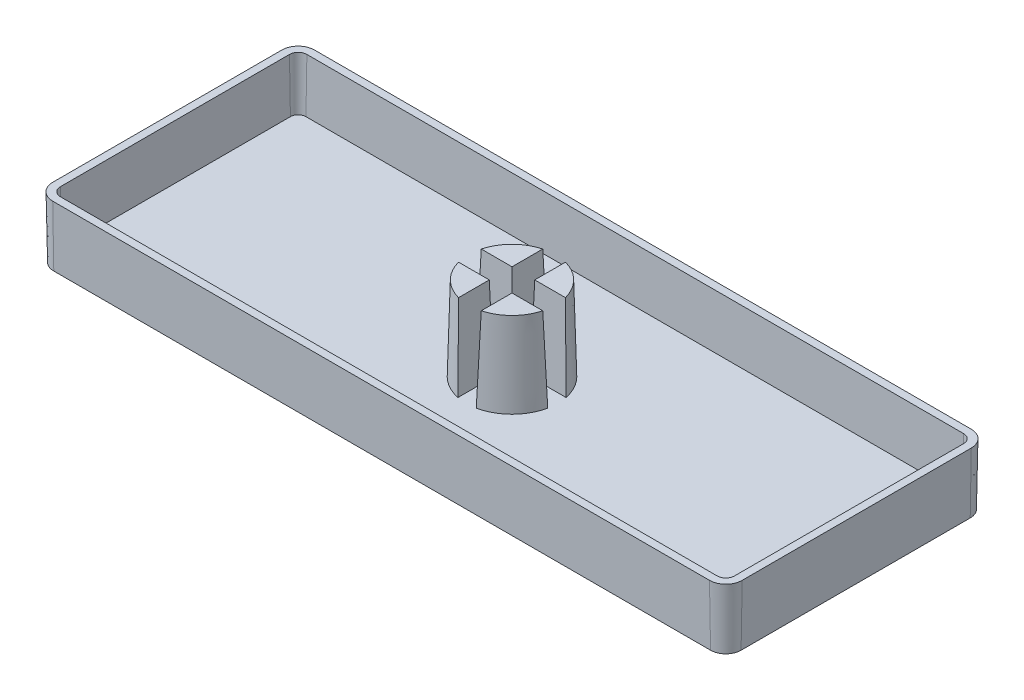
SolidWorks part; units mm, degrees
ref_plane "Front Plane" through (0, 0, 0) normal (0, 0, 1) x (1, 0, 0)
ref_plane "Top Plane" through (0, 0, 0) normal (0, 1, 0) x (1, 0, 0)
ref_plane "Right Plane" through (0, 0, 0) normal (1, 0, 0) x (0, 0, -1)
sketch "Sketch1" plane through (0, 0, 0) normal (0, 1, 0) x (1, 0, 0)
  line L1 (-21.5, -8.5) -> (21.5, -8.5)
  line L2 (-22.5, -7.5) -> (-22.5, 7.5)
  line L3 (-21.5, 8.5) -> (21.5, 8.5)
  line L4 (22.5, -7.5) -> (22.5, 7.5)
  line L5 (-22.5, -8.5) -> (22.5, 8.5) construction
  line L6 (-22.5, 8.5) -> (22.5, -8.5) construction
  arc A0 (-22.5, 7.5) -> (-21.5, 8.5) centre (-21.5, 7.5) cw
  arc A1 (22.5, 7.5) -> (21.5, 8.5) centre (21.5, 7.5) ccw
  arc A2 (22.5, -7.5) -> (21.5, -8.5) centre (21.5, -7.5) cw
  arc A3 (-21.5, -8.5) -> (-22.5, -7.5) centre (-21.5, -7.5) cw
  point P0 (0, 0)
  dimension "D3" = 1
  dimension "D1" = 45
  dimension "D2" = 17
extrude "Boss-Extrude1" add sketch "Sketch1" along normal blind 4 draft 1 draft outward yes
shell "Shell1" thickness 0.5 removed face at (0, 4, 0)
sketch "Sketch2" plane through (0, 0.5, 0) normal (0, 1, 0) x (1, 0, 0)
  line L0 (-0.6, 2.9394) -> (-0.6, 0.6)
  line L1 (0, -2.2) -> (0, 2.2) construction
  line L3 (-2.9394, 0.6) -> (-0.6, 0.6)
  line L4 (-2.2, 0) -> (2.2, 0) construction
  line L5 (-2.9394, -0.6) -> (-0.6, -0.6)
  line L6 (0.6, 2.9394) -> (0.6, 0.6)
  line L7 (-0.6, -0.6) -> (-0.6, -2.9394)
  line L8 (0.6, -0.6) -> (0.6, -2.9394)
  line L9 (0.6, -0.6) -> (2.9394, -0.6)
  line L10 (0.6, 0.6) -> (2.9394, 0.6)
  arc A0 (-2.9394, -0.6) -> (-0.6, -2.9394) centre (0, 0) ccw
  arc A1 (2.9394, 0.6) -> (0.6, 2.9394) centre (0, 0) ccw
  arc A2 (0.6, -2.9394) -> (2.9394, -0.6) centre (0, 0) ccw
  arc A3 (-0.6, 2.9394) -> (-2.9394, 0.6) centre (0, 0) ccw
  dimension "D1" = 0.6
  dimension "D2" = 0.6
extrude "Boss-Extrude2" add sketch "Sketch2" along normal blind 5.5 draft 1.5
